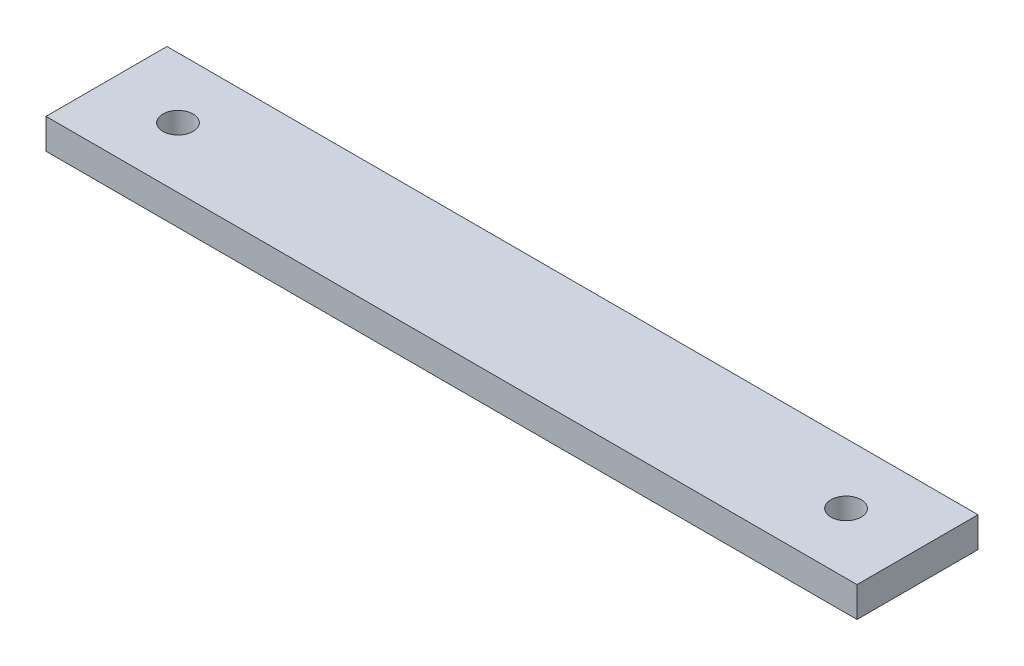
SolidWorks part; units mm, degrees
material "Plain Carbon Steel"
ref_plane "Front Plane" through (0, 0, 0) normal (0, 0, 1) x (1, 0, 0)
ref_plane "Top Plane" through (0, 0, 0) normal (0, 1, 0) x (1, 0, 0)
ref_plane "Right Plane" through (0, 0, 0) normal (1, 0, 0) x (0, 0, -1)
sketch "Sketch1" plane through (0, 0, 0) normal (0, 1, 0) x (1, 0, 0)
  line L1 (-85.1281, 12.7) -> (85.1281, 12.7)
  line L2 (-85.1281, 12.7) -> (-85.1281, -12.7)
  line L3 (-85.1281, -12.7) -> (85.1281, -12.7)
  line L4 (85.1281, 12.7) -> (85.1281, -12.7)
  line L5 (-85.1281, 12.7) -> (85.1281, -12.7) construction
  line L6 (-85.1281, -12.7) -> (85.1281, 12.7) construction
  point P0 (0, 0)
  dimension "D1" = 170.2562
  dimension "D2" = 25.4
extrude "Boss-Extrude1" add sketch "Sketch1" along normal blind 6.35
sketch "Sketch2" plane through (0, 0, 0) normal (0, -1, 0) x (1, 0, 0)
  line L0 (-85.1281, -12.7) -> (-85.1281, 12.7) construction
  line L1 (85.1281, 12.7) -> (85.1281, -12.7) construction
  line L2 (85.1281, -12.7) -> (-85.1281, -12.7) construction
  circle A0 centre (-70.1167, 0) radius 3.175
  circle A1 centre (70.1281, 0) radius 3.175
  dimension "D1" = 15.0114
  dimension "D2" = 15
  dimension "D3" = 12.7
  dimension "D4" = 12.7
  dimension "D5" = 6.35
extrude "Cut-Extrude1" cut sketch "Sketch2" against normal up to next
